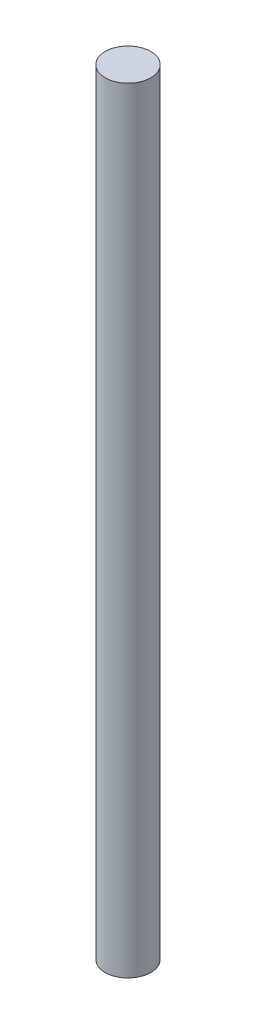
SolidWorks part; units mm, degrees
ref_plane "Front Plane" through (0, 0, 0) normal (0, 0, 1) x (1, 0, 0)
ref_plane "Top Plane" through (0, 0, 0) normal (0, 1, 0) x (1, 0, 0)
ref_plane "Right Plane" through (0, 0, 0) normal (1, 0, 0) x (0, 0, -1)
sketch "Sketch1" plane through (0, 0, 0) normal (0, 1, 0) x (1, 0, 0)
  circle A0 centre (0, 0) radius 2.5
  dimension "D1" = 5
extrude "Boss-Extrude1" add sketch "Sketch1" along normal mid plane 84.9
